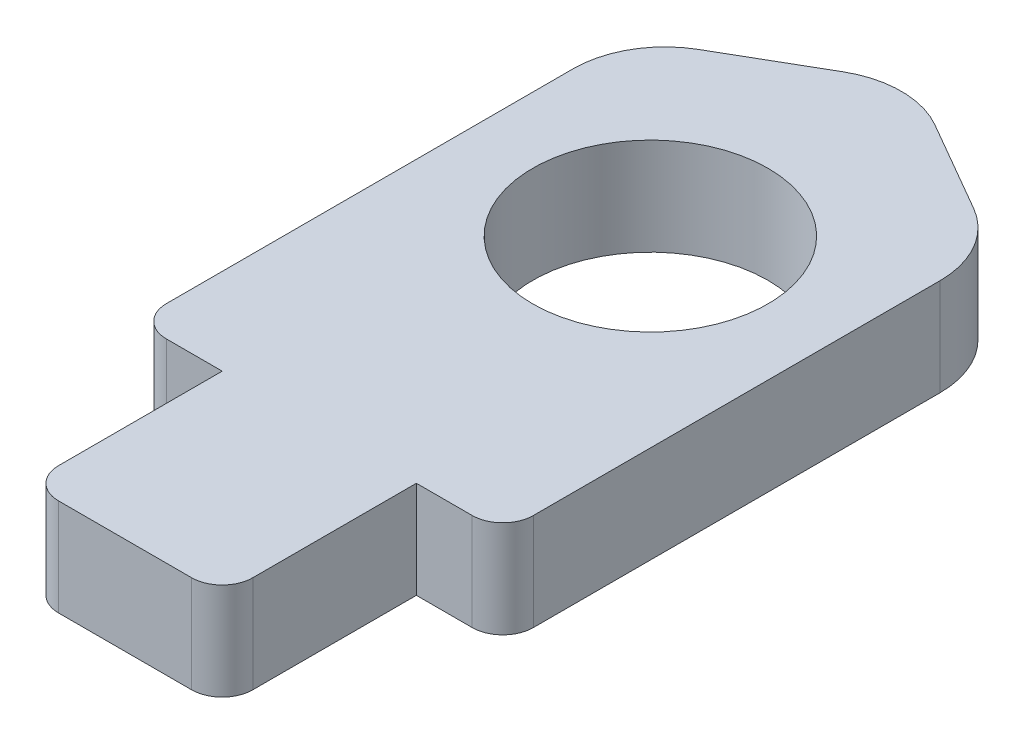
SolidWorks part; units mm, degrees
material "Beech"
ref_plane "Front Plane" through (0, 0, 0) normal (0, 0, 1) x (1, 0, 0)
ref_plane "Top Plane" through (0, 0, 0) normal (0, 1, 0) x (1, 0, 0)
ref_plane "Right Plane" through (0, 0, 0) normal (1, 0, 0) x (0, 0, -1)
sketch "Sketch2" plane through (0, 0, 0) normal (0, 1, 0) x (1, 0, 0)
  line L0 (-6, 5.205) -> (-5.4495, 5.205)
  line L1 (-6, 3.4729) -> (-6, -10.8257)
  line L2 (6, 3.4729) -> (6, -10.8257)
  line L3 (-6, -10.8257) -> (-3.175, -10.8257)
  line L4 (-4.5, 6.071) -> (-1.5, 7.8031)
  line L5 (-3.175, -10.8257) -> (-3.175, -17.1757)
  line L6 (-3.175, -17.1757) -> (3.175, -17.1757)
  line L7 (3.175, -17.1757) -> (3.175, -10.8257)
  line L8 (1.5, 7.8031) -> (4.5, 6.071)
  line L9 (3.175, -10.8257) -> (6, -10.8257)
  line L12 (5.4495, 5.205) -> (6, 5.205)
  circle A0 centre (0, 0) radius 3.845
  arc A1 (-4.5, 6.071) -> (-6, 3.4729) centre (-3, 3.4729) ccw
  arc A2 (4.5, 6.071) -> (6, 3.4729) centre (3, 3.4729) cw
  arc A3 (1.5, 7.8031) -> (-1.5, 7.8031) centre (0, 5.205) ccw
  point P3 (0, 5.205)
  point P14 (0, -17.1757)
  dimension "D1" = 7.69
  dimension "D9" = 3
  dimension "D10" = 3
  dimension "D11" = 3
  dimension "D2" = 5.205
  dimension "D3" = 16.0307
  dimension "D4" = 12
  dimension "D5" = 6.35
  dimension "D6" = 6.35
  dimension "D8" = 30
extrude "MotorMount_Extrude" add sketch "Sketch2" along normal blind 3.175 contours L8 A3 L4 A1 L1 L5 L2 A2 A0 region at (0, 0, 4.7761)
fillet "MotorMount_CornerFillet" radius 1 4 edges at (6, 1.5875, 10.8257) (-6, 1.5875, 10.8257) (-3.175, 1.5875, 17.1757) (3.175, 1.5875, 17.1757)
equation "\"CageLeftBottomEdge\"=22.11mm"
equation "\"CageLeftTopEdge\"=22.11mm"
equation "\"CageRightBottomEdge\"=21.63mm"
equation "\"CageRightTopEdge\"=21.63mm"
equation "\"CageHeight\"=86.04mm"
equation "\"CageLength\"=73.76mm"
equation "\"CageTopScrewClearance\"=10mm"
equation "\"CageBottomScrewClearance\"=25mm"
equation "\"CageLeftTopDepth\"= 11.65mm"
equation "\"CageLeftBottomDepth\"=11.11mm"
equation "\"CageLeftTopHeight\"=8.56175mm"
equation "\"CageLeftBottomHeight\"=16mm"
equation "\"CageRightTopDepth\"= 11.05mm"
equation "\"CageRightBottomDepth\"=10.58mm"
equation "\"CageRightTopHeight\"=9.6mm"
equation "\"CageRightBottomHeight\"=15.49mm"
equation "\"CageLeftTopChannelDepth\"=2.41908mm"
equation "\"CageLeftBottomChannelDepth\"=2.588mm"
equation "\"CageLeftChannelHeight\"=11.7mm"
equation "\"CageRightTopChannelDepth\"=2.32mm"
equation "\"CageRightBottomChannelDepth\"=2.318mm"
equation "\"CageRightChannelHeight\"=10mm"
equation "\"CageChanRelHeight\"=23.99mm"
equation "\"CageChanRelDepth\"=5.492mm"
equation "\"CageChamberRadius\"=16.261mm"
equation "\"CageScrewDiameter\"=4.8mm"
equation "\"CageSetScrewDiameter\"=3.5mm"
equation "\"CageAxleRadius\"=6.639mm"
equation "\"CageAxleKeyHeight\"=1.619mm"
equation "\"CageAxleKeyWidth\"=2.662mm"
equation "\"CageHoseWindowWidth\"=16.29mm"
equation "\"CageHoseWindowHeight\"=26.5mm"
equation "\"CageHoseWindow-Edge\"=8.89mm"
equation "\"CageScrew-VerticalEdge\"=5.0mm"
equation "\"CageScrew-HorizontalEdge\"=7.5mm"
equation "\"CageScrew-HoseCornerScrewEdge\"=4.45mm"
equation "\"CageAxle-BottomEdge\"=56.05mm"
equation "\"CageAxle-FrontEdge\"=46.03mm"
equation "\"CageBackSetScrew-Axle\"=40mm"
equation "\"CageFrontSetScrew-Axle\"=22mm"
equation "\"CageVelocityWindow-BackEdge\"=34.8mm"
equation "\"CageVelocityWindow-BottomEdge\"=27.55mm"
equation "\"CageVelocityWindowHeight\"=22.29mm"
equation "\"CageVelocityWindowWidth\"=12.61mm"
equation "\"TriggerSlot-BottomEdge\"=6.35mm"
equation "\"TriggerSlot-FrontEdge\"=15mm"
equation "\"TriggerSlotSize\"=6.7mm"
equation "\"TriggerRackOffset\"=.236224in"
equation "\"TriggerSlotSizeInt\"=.25in"
equation "\"MotorMountLegLength\"=.25in"
equation "\"GearOffset\"=.264907in"
equation "\"TriggerSlotSpacing\"=.25in"
equation "\"TGMGearFaceDiameter\"=24.40mm"
equation "\"TGMCylinderLength\"=15.00mm"
equation "\"TGMScrewHole-Center\"=8.70mm"
equation "\"TGMScrewHoleDiameter\"=5.04mm"
equation "\"TGMCenterHoleDiameter\"=9.50mm"
equation "\"TGMShaftCollarSideLength\"=19.00mm"
equation "\"TGMShaftCollarDockingDepth\"=7.00mm"
equation "\"whitemotordepth\"=11.27mm"
equation "\"whitemotorbackdepth\"=3.845mm"
equation "\"whitemotoraxledepth\" = 3.5mm"
equation "\"whitemotoraxleoffset\"=11.4mm"
equation "\"whitemotorwidth\"=12.07mm"
equation "\"whitemotorheight\"=16.68mm"
equation "\"whitemotorcylinderlength\" =13.04mm"
equation "\"whitemotorcylinderradius\"=3.845mm"
equation "\"whitemotorcylinderoffset\"=2.35mm"
equation "\"whitemotorcutoutlength\"=1.88mm"
equation "\"whitemotorouterrad\"=5mm"
equation "\"whitemotorinnerrad\"=2.95mm"
equation "\"D1@Sketch2\"=\"whitemotorcylinderradius\"*2"
equation "\"D2@Sketch2\"=\"whitemotoraxleoffset\"-\"whitemotorcylinderradius\"-\"whitemotorcylinderoffset\""
equation "\"D3@Sketch2\"=\"elasticdepth\"+.005in+\"TriggerRackOffset\"+\"GearOffset\""
equation "\"D5@Sketch2\"=\"TriggerSlotSizeInt\""
equation "\"D6@Sketch2\"=\"MotorMountLegLength\""
equation "\"motormountwidth\"=12mm"
equation "\"D4@Sketch2\"=\"motormountwidth\""
equation "\"TriggerMiniSlotWidth\"=3.5mm"
equation "\"TriggerRackWidth\"=6.5mm"
equation "\"elasticracklength\"=2in"
equation "\"elasticrackpegsize\"=.25in"
equation "\"elasticrackpegbuffer\"=.125in"
equation "\"elasticrackpegspacing\"=1.76476378in"
equation "\"elasticbaybuffer\"=.25in"
equation "\"elasticdepth\"=.125in"
equation "\"motormountcornerfillet\"=3mm"
equation "\"D10@Sketch2\"=\"motormountcornerfillet\""
equation "\"elasticbaydepth\"=.75in"
equation "\"pandiscradius\"=14in"
equation "\"towermaterialwidth\"=.25in"
equation "\"towerslotlength\"=.5in"
equation "\"towermarkerspace\"=5in"
equation "\"towerslothorizoffset\"=1in"
equation "\"towerslothorizspacing\"=2in"
equation "\"towerslotvertoffset\"=3in"
equation "\"towerslotvertspacing\"=2in"
equation "\"towerheight\"=12in"
equation "\"towerupslot\"=1in"
equation "\"toweraxle\"=.5in"
equation "\"towerplatslotoffset\"=1.5in"
equation "\"towermotorpanelheight\"=10in"
equation "\"towerplatdepth\"=2in"
equation "\"stepperouterrad\"=10mm"
equation "\"stepperscrewsize\"=3.45mm"
equation "\"stepperscrewc2c\"=49.5mm"
equation "\"stepperdepthoffset\"=24mm"
equation "\"stepperhorizoffset\"=22.91mm"
